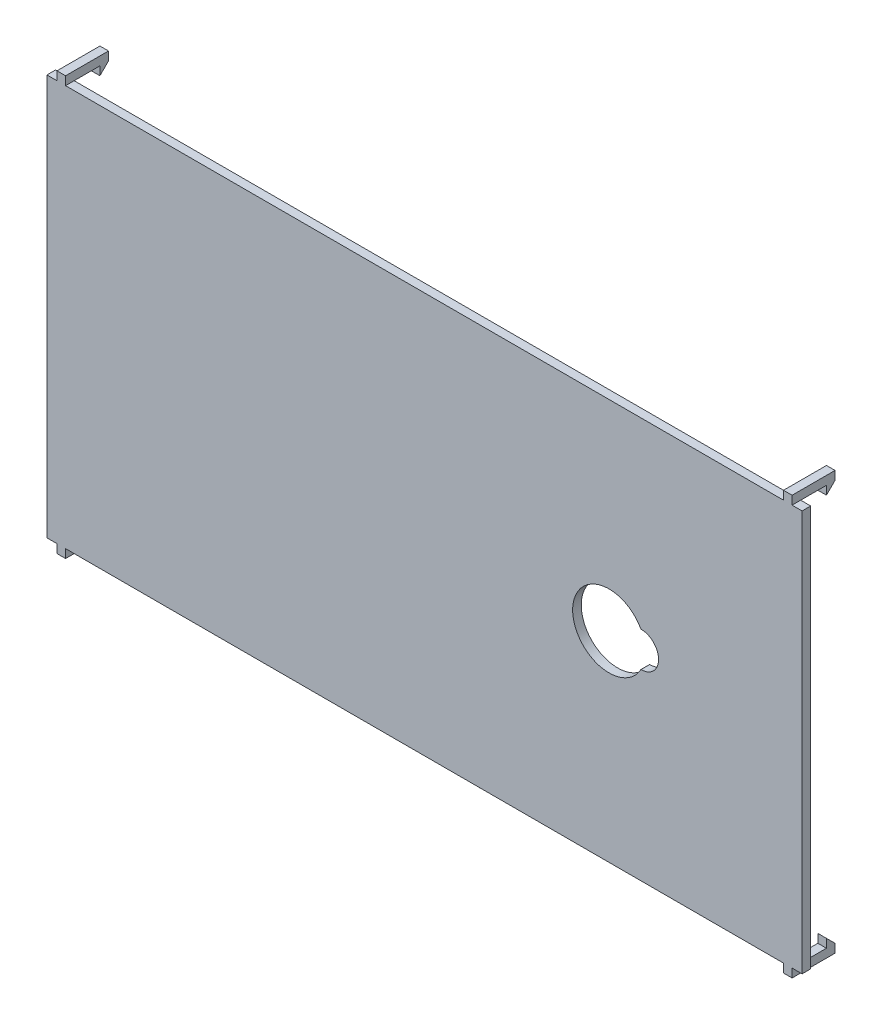
SolidWorks part; units mm, degrees
ref_plane "Front Plane" through (0, 0, 0) normal (0, 0, 1) x (1, 0, 0)
ref_plane "Top Plane" through (0, 0, 0) normal (0, 1, 0) x (1, 0, 0)
ref_plane "Right Plane" through (0, 0, 0) normal (1, 0, 0) x (0, 0, -1)
sketch "Sketch1" plane through (0, 0, 0) normal (0, 0, 1) x (1, 0, 0)
  line L0 (121.1, -9.75) -> (-10.75, -9.75)
  line L1 (119.6, -8.25) -> (-9.25, -8.25)
  line L2 (119.6, -8.25) -> (119.6, 58.75)
  line L3 (119.6, 58.75) -> (-9.25, 58.75)
  line L4 (-9.25, -8.25) -> (-9.25, 58.75)
  line L5 (-10.75, -9.75) -> (-10.75, 60.25)
  line L6 (121.1, 60.25) -> (-10.75, 60.25)
  line L7 (121.1, -9.75) -> (121.1, 60.25)
  dimension "D1" = 1.5
extrude "Boss-Extrude1" add sketch "Sketch1" along normal blind 1.5 contours L7 L6 L5 L0
sketch "Sketch2" plane through (0, 0, 1.5) normal (0, 0, 1) x (1, 0, 0)
  line L5 (92.9571, 22.2) -> (92.9875, 22.2)
  line L6 (92.9875, 28.3) -> (92.9571, 28.3)
  line L7 (92.9571, 22.2) -> (92.9875, 22.2)
  line L8 (92.9875, 28.3) -> (92.9571, 28.3)
  arc A10 (92.9875, 22.2) -> (92.9875, 28.3) centre (92.9875, 25.25) ccw
  arc A11 (92.9571, 28.3) -> (92.9571, 22.2) centre (87.3875, 25.25) ccw
  arc A12 (92.9875, 22.2) -> (92.9875, 28.3) centre (92.9875, 25.25) ccw
  arc A13 (92.9571, 28.3) -> (92.9571, 22.2) centre (87.3875, 25.25) ccw
  dimension "D1" = 0.25
extrude "Cut-Extrude1" cut sketch "Sketch2" against normal up to next
ref_plane "Plane2" through (0, 25.25, 0) normal (0, 1, 0) x (1, 0, 0)
ref_plane "Plane1" through (55.175, 0, 0) normal (1, 0, 0) x (0, 0, -1)
sketch "Sketch3" plane through (121.1, 0, 0) normal (1, 0, 0) x (0, 0, -1)
  line L0 (0, -9.75) -> (0, 60.25) construction
  line L1 (-1.5, 60.25) -> (6, 60.25)
  line L2 (-1.5, 60.25) -> (-1.5, 61.75)
  line L3 (-1.5, 61.75) -> (6, 61.75)
  line L4 (6, 60.25) -> (6, 61.75)
  line L5 (6, 60.25) -> (4.5, 58.75)
  line L7 (4.5, 58.75) -> (4.5, 60.25)
  line M6 (0, 60.25) -> (-1.5, 60.25)
  dimension "D1" = 1.5
  dimension "D2" = 6
  dimension "D3" = 45
extrude "Boss-Extrude2" add sketch "Sketch3" against normal blind 1.5 from offset 1.75 contours L1 L4 L3 L2 M6 | L7 L5 L1 region at (121.1, 61, -2.25) region at (121.1, 59.75, -5) offset against normal yes
mirror "Mirror1" about plane through (55.175, 0, 0) normal (1, 0, 0) of "Boss-Extrude2"
mirror "Mirror2" about plane through (0, 25.25, 0) normal (0, 1, 0) of "Mirror1", "Boss-Extrude2"
equation "\"D1@Boss-Extrude2\"=1.50mm+.25"
equation "\"D19@Boss-Extrude2\"=1.50mm+.25"
